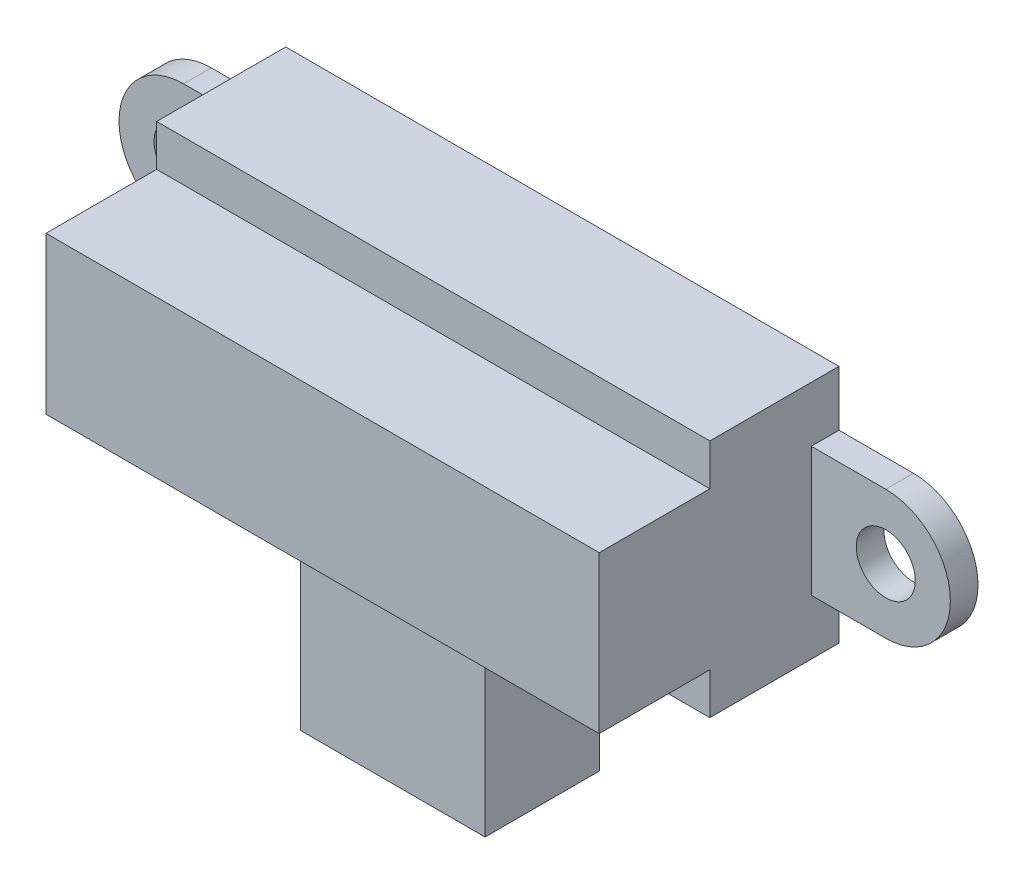
SolidWorks part; units mm, degrees
ref_plane "Front Plane" through (0, 0, 0) normal (0, 0, 1) x (1, 0, 0)
ref_plane "Top Plane" through (0, 0, 0) normal (0, 1, 0) x (1, 0, 0)
ref_plane "Right Plane" through (0, 0, 0) normal (1, 0, 0) x (0, 0, -1)
sketch "Sketch1" plane through (0, 0, 0) normal (0, 0, 1) x (1, 0, 0)
  line L0 (15, 0) -> (15, 13) construction
  line L1 (0, 0) -> (15, 0)
  line L2 (0, 0) -> (0, 3)
  line L3 (0, 13) -> (15, 13)
  line L4 (0, 10) -> (0, 13)
  line L5 (0, 10) -> (-4.041, 10)
  line L6 (0, 10) -> (0, 3)
  line L7 (0, 3) -> (-4.041, 3)
  arc A0 (-4.041, 10) -> (-4.041, 3) centre (-4.041, 6.5) ccw
  circle A1 centre (-4.041, 6.5) radius 1.6
  dimension "D1" = 15
  dimension "D2" = 3
  dimension "D3" = 3
  dimension "D4" = 13
extrude "Boss-Extrude1" add sketch "Sketch1" along normal blind 7 contours L1 L0 L3 L4 L5 A0 L7 L2 A1 region at (7.5, 6.5, 0)
extrude "Boss-Extrude2" add sketch "Sketch1<3>" along normal blind 1.5 contours L5 A0 L7 L6 A1 region at (-0.1029, 6.5, 0)
sketch "Sketch1<3>" plane through (0, 0, 0) normal (0, 0, 1) x (1, 0, 0) same geometry as "Sketch1"
mirror "Mirror1" about plane through (15, -13.8811, 7) normal (-1, 0, 0) of "Boss-Extrude1", "Boss-Extrude2"
sketch "Sketch2" plane through (0, 0, 7) normal (0, 0, 1) x (1, 0, 0)
  line L0 (0, 0) -> (0, 13) construction
  line L1 (0, 10.75) -> (30, 10.75)
  line L2 (0, 10.75) -> (0, 2.25)
  line L3 (0, 2.25) -> (30, 2.25)
  line L4 (30, 10.75) -> (30, 2.25)
  line L5 (30, 0) -> (30, 13) construction
  point P8 (0, 6.5)
  point P9 (0, 6.5)
  dimension "D1" = 8.5
extrude "Boss-Extrude3" add sketch "Sketch2" along normal blind 6
sketch "Sketch3" plane through (0, 0, 0) normal (0, -1, 0) x (1, 0, 0)
  line L0 (0, 0) -> (30, 0) construction
  line L1 (9.5103, 8.7) -> (19.5103, 8.7)
  line L2 (9.5103, 8.7) -> (9.5103, 2.5)
  line L3 (9.5103, 2.5) -> (19.5103, 2.5)
  line L4 (19.5103, 8.7) -> (19.5103, 2.5)
  dimension "D1" = 2.5
  dimension "D2" = 6.2
  dimension "D3" = 10
extrude "Boss-Extrude4" add sketch "Sketch3" along normal blind 10 and the other way blind 6
